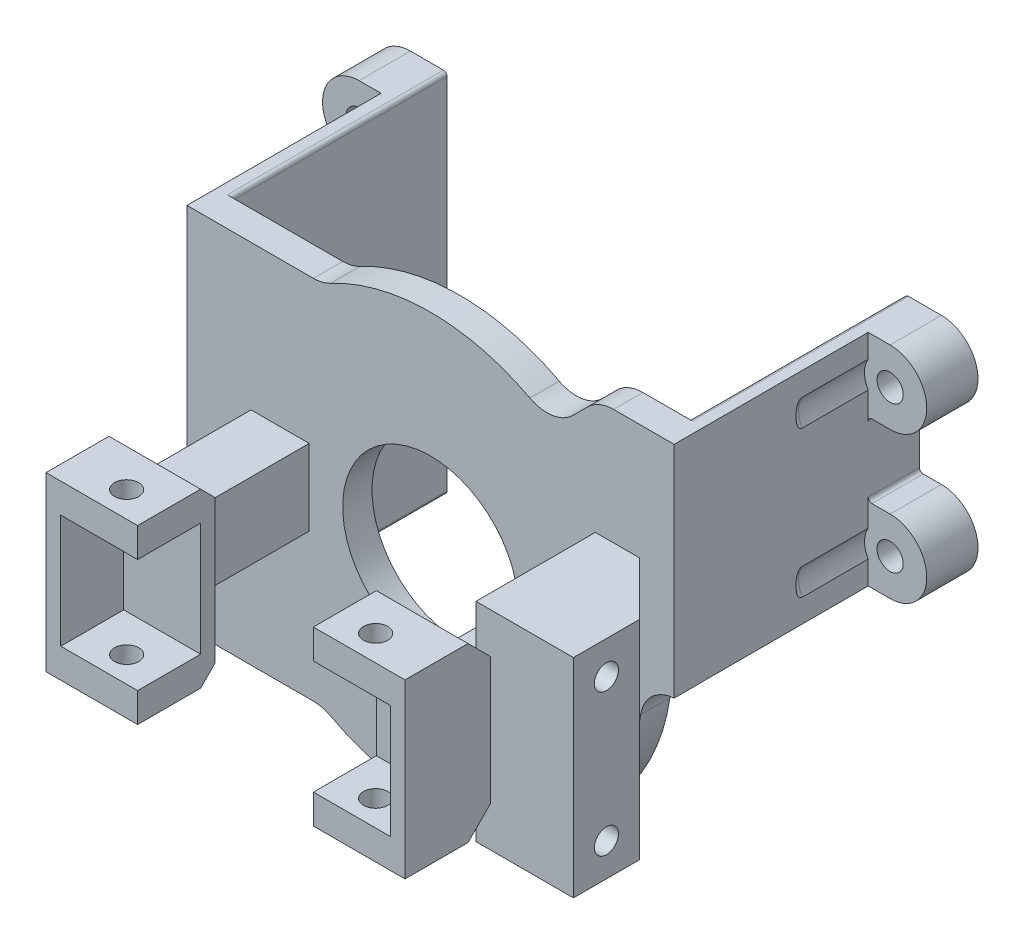
SolidWorks part; units mm, degrees
ref_plane "Front Plane" through (0, 0, 0) normal (0, 0, 1) x (1, 0, 0)
ref_plane "Top Plane" through (0, 0, 0) normal (0, 1, 0) x (1, 0, 0)
ref_plane "Right Plane" through (0, 0, 0) normal (1, 0, 0) x (0, 0, -1)
sketch "Sketch1" plane through (0, 0, 0) normal (0, 0, 1) x (1, 0, 0)
  line L22 (36.25, 10.0017) -> (33.76, 10.0017)
  line L27 (33.26, 19.5) -> (33.26, 10.5017)
  line L33 (-36.25, 15) -> (-33.76, 15)
  line L35 (-36.25, -15) -> (-33.76, -15)
  line L40 (36.25, 20) -> (33.76, 20)
  line L50 (-33.26, -14.5) -> (-33.26, 14.5)
  line L56 (36.25, 0.0017) -> (33.6306, 0.0017)
  line L57 (-36.25, -25) -> (-16, -25)
  line L60 (-36.25, 25) -> (-16, 25)
  line L65 (19.4427, 26.5138) -> (21.4645, 28.5355)
  line L66 (36.25, 30) -> (25, 30)
  circle A3 centre (-36.25, 20) radius 1.79
  circle A4 centre (-36.25, -20) radius 1.79
  arc A7 (-36.25, 25) -> (-36.25, 15) centre (-36.25, 20) ccw
  arc A8 (-36.25, -15) -> (-36.25, -25) centre (-36.25, -20) ccw
  arc A9 (36.25, 20) -> (36.25, 30) centre (36.25, 25) ccw
  arc A23 (33.76, 20) -> (33.26, 19.5) centre (33.76, 19.5) ccw
  arc A28 (-33.76, -15) -> (-33.26, -14.5) centre (-33.76, -14.5) ccw
  arc A29 (-33.76, 15) -> (-33.26, 14.5) centre (-33.76, 14.5) cw
  arc A35 (33.76, 10.0017) -> (33.26, 10.5017) centre (33.76, 10.5017) cw
  circle A36 centre (36.25, 5.0017) radius 1.79
  circle A37 centre (0, 0) radius 12
  circle A53 centre (36.25, 25) radius 1.79
  arc A54 (13.5679, 25.6303) -> (-13.6471, 25.5882) centre (0, 0) ccw
  arc A55 (36.25, 0.0017) -> (36.25, 10.0017) centre (36.25, 5.0017) ccw
  arc A56 (-13.6471, -25.5882) -> (28.6849, -4.2633) centre (0, 0) ccw
  arc A57 (-16, 25) -> (-13.6471, 25.5882) centre (-16, 30) ccw
  arc A58 (-13.6471, -25.5882) -> (-16, -25) centre (-16, -30) ccw
  arc A59 (33.6306, 0.0017) -> (28.6849, -4.2633) centre (33.6306, -4.9983) ccw
  arc A63 (19.4427, 26.5138) -> (13.5679, 25.6303) centre (15.9072, 30.0493) cw
  arc A64 (25, 30) -> (21.4645, 28.5355) centre (25, 25) ccw
extrude "Boss-Extrude1" add sketch "Sketch1" along normal blind 61.5
sketch "Sketch2" plane through (0, 0, 0) normal (0, 0, 1) x (1, 0, 0)
  line L9 (31.25, 30) -> (-31.25, 30)
  line L10 (31.25, 29.5) -> (31.25, 0.5017)
  line L14 (-31.25, -30) -> (31.25, -30)
  line L15 (31.25, -30) -> (31.25, -0.6014)
  line L16 (33.6306, 0.0017) -> (31.75, 0.0017)
  line L55 (31.75, 30) -> (31.25, 30)
  line L59 (-31.25, 25) -> (-31.75, 25)
  line L62 (-31.25, -25) -> (-31.75, -25)
  line L63 (-31.25, 30) -> (-31.25, 25)
  line L64 (-31.25, 24.5) -> (-31.25, -24.5)
  line L65 (-31.25, -25) -> (-31.25, -30)
  arc A13 (31.75, 30) -> (31.25, 29.5) centre (31.75, 29.5) ccw
  arc A18 (31.75, 0.0017) -> (31.25, 0.5017) centre (31.75, 0.5017) cw
  arc A19 (33.6306, 0.0017) -> (31.25, -0.6014) centre (33.6306, -4.9983) ccw
  arc A20 (-31.25, 24.5) -> (-31.75, 25) centre (-31.75, 24.5) ccw
  arc A21 (-31.75, -25) -> (-31.25, -24.5) centre (-31.75, -24.5) ccw
extrude "Cut-Extrude1" cut sketch "Sketch2" along normal blind 29.5
sketch "Sketch3" plane through (0, 0, 61.5) normal (0, 0, 1) x (1, 0, 0)
  line L16 (36.25, 10.0017) -> (33.76, 10.0017)
  line L18 (33.26, 30) -> (36.25, 30)
  line L19 (36.25, 20) -> (33.76, 20)
  line L24 (-33.76, -15) -> (-36.25, -15)
  line L29 (-36.25, 15) -> (-33.76, 15)
  line L30 (-33.26, 14.5) -> (-33.26, 25)
  line L31 (-33.26, -25) -> (-33.26, -14.5)
  line L32 (33.26, 10.5017) -> (33.26, -0.0121)
  line L33 (33.26, 19.5) -> (33.26, 30)
  line L34 (36.25, 0.0017) -> (33.6306, 0.0017)
  line L35 (-36.25, 25) -> (-33.26, 25)
  line L37 (-36.25, -25) -> (-33.26, -25)
  arc A15 (33.26, 10.5017) -> (33.76, 10.0017) centre (33.76, 10.5017) ccw
  arc A18 (36.25, 20) -> (36.25, 30) centre (36.25, 25) ccw
  arc A20 (33.76, 20) -> (33.26, 19.5) centre (33.76, 19.5) ccw
  arc A22 (-36.25, -15) -> (-36.25, -25) centre (-36.25, -20) ccw
  arc A23 (-33.76, -15) -> (-33.26, -14.5) centre (-33.76, -14.5) ccw
  arc A25 (-33.26, 14.5) -> (-33.76, 15) centre (-33.76, 14.5) ccw
  arc A26 (-36.25, 25) -> (-36.25, 15) centre (-36.25, 20) ccw
  arc A28 (36.25, 0.0017) -> (36.25, 10.0017) centre (36.25, 5.0017) ccw
  arc A29 (33.6306, 0.0017) -> (33.26, -0.0121) centre (33.6306, -4.9983) ccw
extrude "Cut-Extrude2" cut sketch "Sketch3" against normal offset from surface (54.5 mm away) 7 up to face at (38.04, 25, 0)
sketch "Sketch4" plane through (0, 0, 61.5) normal (0, 0, 1) x (1, 0, 0)
  line L1 (-12, 11.77) -> (-24.51, 11.77)
  line L2 (-22.5, -7.75) -> (-12, -7.75)
  line L4 (-22.5, 7.75) -> (-12, 7.75)
  line L5 (-12, -11.77) -> (-24.51, -11.77)
  line L6 (12, -11.77) -> (24.51, -11.77)
  line L11 (12, -11.77) -> (12, -7.75)
  line L13 (12, 7.75) -> (12, 11.77)
  line L14 (-22.5, -7.75) -> (-22.5, 7.75)
  line L15 (-12, 7.75) -> (-12, 11.77)
  line L16 (-12, -11.77) -> (-12, -7.75)
  line L24 (12, -7.75) -> (22.5, -7.75)
  line L26 (12, 7.75) -> (22.5, 7.75)
  line L27 (-24.51, -11.77) -> (-24.51, 11.77)
  line L30 (24.51, -11.77) -> (24.51, 11.77)
  line L32 (22.5, -7.75) -> (22.5, 7.75)
  line L35 (24.51, 11.77) -> (12, 11.77)
extrude "Cut-Extrude3" cut sketch "Sketch4" against normal blind 8.6 flip side to cut
sketch "Sketch5" plane through (0, 11.77, 0) normal (0, 1, 0) x (1, 0, 0)
  circle A2 centre (17, -58) radius 1.65
  circle A3 centre (-17, -58) radius 1.65
extrude "Cut-Extrude4" cut sketch "Sketch5" against normal up to surface (23.54 mm away) up to face at (-18.255, -11.77, 57.2)
sketch "Sketch15" plane through (0, 0, 52.9) normal (0, 0, 1) x (1, 0, 0)
  line L1 (-41.25, -29) -> (41.25, -29)
  line L2 (-41.25, -29) -> (-41.25, 30)
  line L3 (-41.25, 30) -> (41.25, 30)
  line L4 (41.25, -29) -> (41.25, 30)
extrude "Cut-Extrude7" cut sketch "Sketch15" against normal offset from surface (19.4 mm away) 4 up to face at (12, 0, 29.5)
sketch "Sketch10" plane through (0, 0, 0) normal (0, 1, 0) x (1, 0, 0)
  line L3 (24.51, -29.5) -> (35.81, -40.8)
  line L5 (35.81, -49.8) -> (35.81, -40.8)
  line L8 (22.5, -49.8) -> (22.5, -29.5)
  line L9 (22.5, -49.8) -> (35.81, -49.8)
  line L10 (22.5, -29.5) -> (24.51, -29.5)
extrude "Boss-Extrude5" add sketch "Sketch10" along normal mid plane 28.42
sketch "Sketch8" plane through (0, 0, 7) normal (0, 0, 1) x (1, 0, 0)
  circle A0 centre (36.25, 5.0017) radius 3.5
  circle A1 centre (36.25, 25) radius 3.5
  circle A2 centre (-36.25, 20) radius 3.5
  circle A3 centre (-36.25, -20) radius 3.5
sketch "Sketch13" plane through (35.81, 0, 0) normal (1, 0, 0) x (0, 0, -1)
  circle A0 centre (-45.3, 9.7) radius 1.65
  circle A1 centre (-45.3, -9.7) radius 1.65
extrude "Cut-Extrude8" cut sketch "Sketch13" against normal up to surface (13.31 mm away) up to face at (22.5, 0, 41.65)
sketch "Sketch16" plane through (22.5, 0, 0) normal (-1, 0, 0) x (0, 0, 1)
  line L1 (48.6486, 9.7) -> (46.9743, 12.6)
  line L2 (46.9743, 12.6) -> (43.6257, 12.6)
  line L3 (43.6257, 12.6) -> (41.9514, 9.7)
  line L4 (41.9514, 9.7) -> (43.6257, 6.8)
  line L5 (43.6257, 6.8) -> (46.9743, 6.8)
  line L6 (46.9743, 6.8) -> (48.6486, 9.7)
  line L7 (48.6486, -9.7) -> (46.9743, -6.8)
  line L8 (46.9743, -6.8) -> (43.6257, -6.8)
  line L9 (43.6257, -6.8) -> (41.9514, -9.7)
  line L10 (41.9514, -9.7) -> (43.6257, -12.6)
  line L11 (43.6257, -12.6) -> (46.9743, -12.6)
  line L12 (46.9743, -12.6) -> (48.6486, -9.7)
extrude "Cut-Extrude9" cut sketch "Sketch16" against normal offset from surface (10.31 mm away) 3 up to face at (35.81, 9.7, 43.65)
sketch "Sketch18" plane through (24.51, 0, 0) normal (1, 0, 0) x (0, 0, -1)
  line L0 (-52.9, 11.77) -> (-46.32, 5.19)
  line L2 (-46.32, 5.19) -> (-33.5, 5.19)
  line L4 (-33.5, 5.19) -> (-33.5, -5.19)
  line L6 (-33.5, -5.19) -> (-46.32, -5.19)
  line L8 (-46.32, -5.19) -> (-52.9, -11.77)
  line L9 (-52.9, -11.77) -> (-52.9, 11.77)
extrude "Boss-Extrude6" add sketch "Sketch18" against normal up to surface (12.51 mm away) up to face at (12, 9.76, 57.2)
extrude "Boss-Extrude7" add sketch "Sketch18<2>" along normal up to surface (-36.51 mm away) from surface up to face at (-12, 9.76, 57.2) starting at face at (-24.51, 0, 57.2)
sketch "Sketch18<2>" plane through (24.51, 0, 0) normal (1, 0, 0) x (0, 0, -1) same geometry as "Sketch18"
sketch "Sketch19" plane through (0, 0, 0) normal (0, 1, 0) x (1, 0, 0)
  line L8 (-16.58, -33.5) -> (16.58, -33.5)
  line L20 (12, -50.9) -> (-12, -50.9)
  line L22 (-12, -50.9) -> (-16.58, -46.32)
  line L24 (-16.58, -46.32) -> (-16.58, -33.5)
  line L26 (12, -50.9) -> (16.58, -46.32)
  line L28 (16.58, -46.32) -> (16.58, -33.5)
extrude "Cut-Extrude10" cut sketch "Sketch19" along normal up to surface (11.77 mm away) from surface up to face at (17, 11.77, 59.65) starting at face at (17, -11.77, 56.35)
extrude "Cut-Extrude11" cut sketch "Sketch8" along normal blind 10
fillet "Fillet2" radius 1 4 edges at (-32.75, -20, 17) (-32.75, 20, 17) (32.75, 25, 17) (32.75, 5.0017, 17)
sketch "Sketch20" plane through (-33.26, 0, 0) normal (-1, 0, 0) x (0, 0, 1)
  circle A0 centre (14, 0) radius 4
extrude "Cut-Extrude12" cut sketch "Sketch20" against normal up to surface (2.01 mm away) contours A0 up to face at (-31.25, 0, 14.75)
